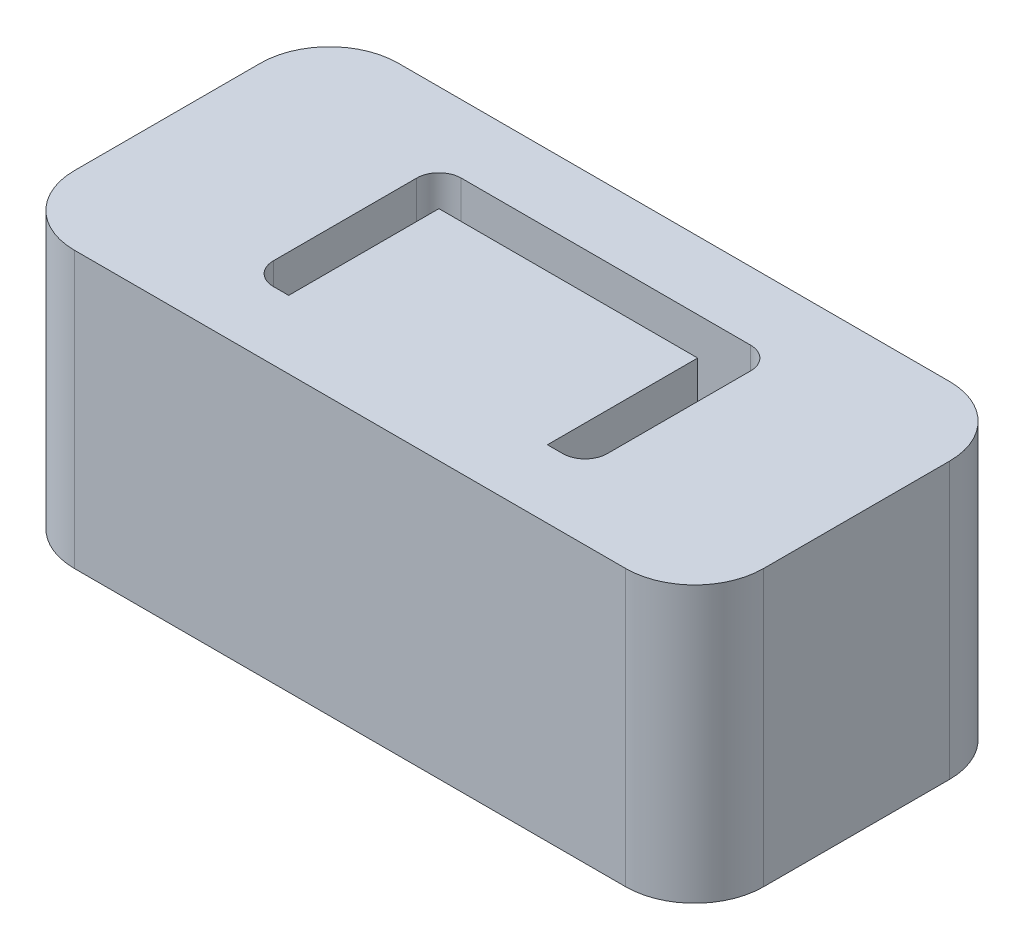
SolidWorks part; units mm, degrees
material "K110"
ref_plane "Front Plane" through (0, 0, 0) normal (0, 0, 1) x (1, 0, 0)
ref_plane "Top Plane" through (0, 0, 0) normal (0, 1, 0) x (1, 0, 0)
ref_plane "Right Plane" through (0, 0, 0) normal (1, 0, 0) x (0, 0, -1)
sketch "Sketch2" plane through (0, 0, 0) normal (0, 1, 0) x (1, 0, 0)
  line L1 (-50, -23.5) -> (50, -23.5)
  line L2 (-50, -23.5) -> (-50, 23.5)
  line L3 (-50, 23.5) -> (50, 23.5)
  line L4 (50, -23.5) -> (50, 23.5)
  line L5 (-50, -23.5) -> (50, 23.5) construction
  line L6 (-50, 23.5) -> (50, -23.5) construction
  point P0 (0, 0)
  dimension "D1" = 100
  dimension "D2" = 47
extrude "Boss-Extrude1" add sketch "Sketch2" against normal blind 40
fillet "Fillet1" radius 10 4 edges at (-50, -20, -23.5) (50, -20, -23.5) (50, -20, 23.5) (-50, -20, 23.5)
sketch "Sketch3" plane through (0, 0, 0) normal (0, 1, 0) x (1, 0, 0)
  line L16 (24.23, -10.4) -> (24.23, 10.4)
  line L17 (18.77, -13.63) -> (21, -13.63)
  line L18 (18.77, 8.17) -> (18.77, -13.63)
  line L19 (-18.77, 8.17) -> (18.77, 8.17)
  line L20 (-18.77, -13.63) -> (-18.77, 8.17)
  line L21 (-21, -13.63) -> (-18.77, -13.63)
  line L22 (-24.23, 10.4) -> (-24.23, -10.4)
  line L23 (21, 13.63) -> (-21, 13.63)
  line L24 (24.23, -10.4) -> (24.23, 10.4)
  line L25 (18.77, -13.63) -> (21, -13.63)
  line L26 (18.77, 8.17) -> (18.77, -13.63)
  line L27 (-18.77, 8.17) -> (18.77, 8.17)
  line L28 (-18.77, -13.63) -> (-18.77, 8.17)
  line L29 (-21, -13.63) -> (-18.77, -13.63)
  line L30 (-24.23, 10.4) -> (-24.23, -10.4)
  line L31 (21, 13.63) -> (-21, 13.63)
  arc A8 (24.23, 10.4) -> (21, 13.63) centre (21, 10.4) ccw
  arc A9 (21, -13.63) -> (24.23, -10.4) centre (21, -10.4) ccw
  arc A10 (-24.23, -10.4) -> (-21, -13.63) centre (-21, -10.4) ccw
  arc A11 (-21, 13.63) -> (-24.23, 10.4) centre (-21, 10.4) ccw
  arc A12 (24.23, 10.4) -> (21, 13.63) centre (21, 10.4) ccw
  arc A13 (21, -13.63) -> (24.23, -10.4) centre (21, -10.4) ccw
  arc A14 (-24.23, -10.4) -> (-21, -13.63) centre (-21, -10.4) ccw
  arc A15 (-21, 13.63) -> (-24.23, 10.4) centre (-21, 10.4) ccw
  dimension "D1" = 0.23
extrude "Cut-Extrude1" cut sketch "Sketch3" against normal up to next
hole_wizard "M6 Tapped Hole1" positions "Sketch6" profile "Sketch5" tap size "M6" standard "ISO"
sketch "Sketch6" plane through (0, -40, 0) normal (0, -1, 0) x (-1, 0, 0)
  line L0 (-50, -13.5) -> (-50, 13.5) construction
  line L1 (-40, 23.5) -> (40, 23.5) construction
  line L2 (40, -23.5) -> (-40, -23.5) construction
  line L3 (50, 13.5) -> (50, -13.5) construction
  point P0 (-43, 16.5)
  point P2 (43, 16.5)
  point P4 (43, -16.5)
  point P6 (-43, -16.5)
  dimension "D1" = 7
  dimension "D2" = 7
  dimension "D3" = 7
  dimension "D4" = 7
sketch "Sketch5" plane through (43, -40, -16.5) normal (1, 0, 0) x (0, 0, -1)
  line L0 (0, 0) -> (0, 18.5022)
  line L1 (0, 18.5022) -> (2.5, 17)
  line L2 (2.5, 17) -> (2.5, 0.525)
  line L3 (2.5, 0.525) -> (3.025, 0)
  line L5 (3.025, 0) -> (0, 0)
  line L6 (-2.5, 0.525) -> (-3.025, 0) construction
  line L10 (0, 18.5022) -> (-2.5, 17) construction
  line L11 (0, -6.35) -> (0, 107.95) construction
  dimension "Tap Drill Dia." = 5
  dimension "Tap Drill Depth" = 17
  dimension "Near C'Sink Dia." = 6.05
  dimension "Near C'Sink Angle" = 90
  dimension "Drill Angle" = 118
cosmetic thread "Hole Thread1"
cosmetic thread "Hole Thread2"
cosmetic thread "Hole Thread3"
cosmetic thread "Hole Thread4"
